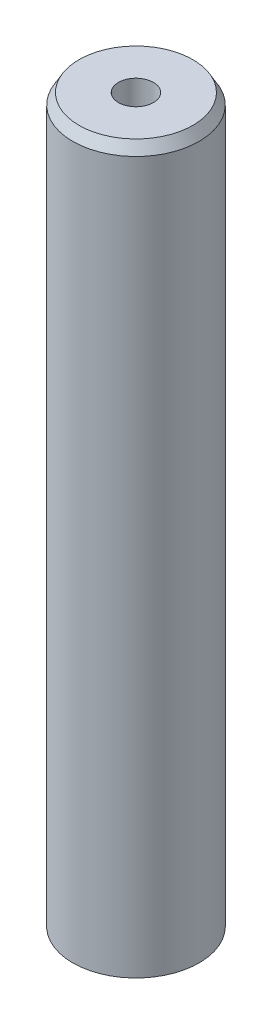
SolidWorks part; units mm, degrees
ref_plane "Front Plane" through (0, 0, 0) normal (0, 0, 1) x (1, 0, 0)
ref_plane "Top Plane" through (0, 0, 0) normal (0, 1, 0) x (1, 0, 0)
ref_plane "Right Plane" through (0, 0, 0) normal (1, 0, 0) x (0, 0, -1)
sketch "Sketch1" plane through (0, 0, 0) normal (0, 1, 0) x (1, 0, 0)
  circle A0 centre (0, 0) radius 7.5
  dimension "SHAFT_OD" = 15
extrude "Boss-Extrude1" add sketch "Sketch1" along normal blind 86.4883
sketch "Sketch2" plane through (0, 0, 0) normal (0, 1, 0) x (1, 0, 0)
  circle A0 centre (0, 0) radius 2.0792
  dimension "BORE_D" = 4.1585
extrude "Cut-Extrude1" cut sketch "Sketch2" along normal through all
chamfer "Chamfer1" distance 1.2808 angle 30 2 edges at (0, 86.4883, 7.5) (0, 0, 7.5) first distance on face at (0, 86.4883, 7.5) first distance on face at (0, 0, 2.0792)
